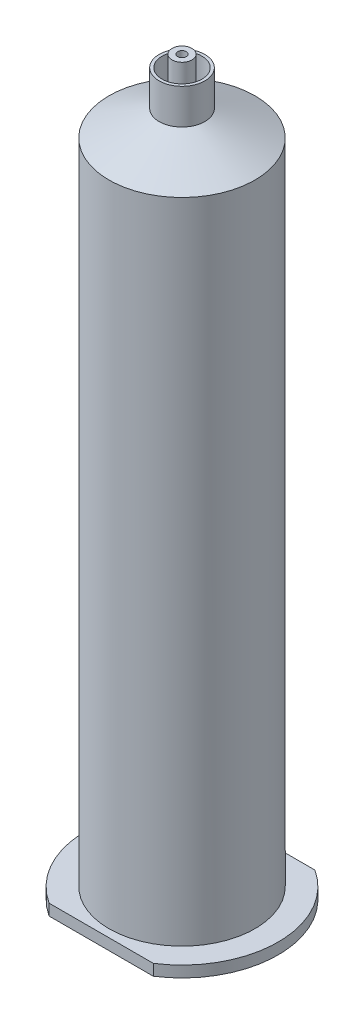
SolidWorks part; units mm, degrees
material "ABS"
ref_plane "Front Plane" through (0, 0, 0) normal (0, 0, 1) x (1, 0, 0)
ref_plane "Top Plane" through (0, 0, 0) normal (0, 1, 0) x (1, 0, 0)
ref_plane "Right Plane" through (0, 0, 0) normal (1, 0, 0) x (0, 0, -1)
sketch "Sketch3" plane through (0, 0, 0) normal (0, 1, 0) x (1, 0, 0)
  line L1 (-16.6, 16.6) -> (16.6, 16.6) construction
  line L2 (-16.6, 16.6) -> (-16.6, -16.6) construction
  line L3 (-16.6, -16.6) -> (16.6, -16.6) construction
  line L4 (16.6, 16.6) -> (16.6, -16.6) construction
  line L5 (-16.6, 16.6) -> (16.6, -16.6) construction
  line L6 (-16.6, -16.6) -> (16.6, 16.6) construction
  line L8 (-10.7006, 16.6) -> (10.7006, 16.6)
  line L9 (0, 0) -> (0, 16.6) construction
  line L26 (-10.7006, -16.6) -> (10.7006, -16.6)
  arc A18 (-10.7006, 16.6) -> (-10.7006, -16.6) centre (0, 0) ccw
  arc A19 (10.7006, -16.6) -> (10.7006, 16.6) centre (0, 0) ccw
  point P0 (0, 0)
  dimension "D1" = 39.5
  dimension "D2" = 33.2
extrude "Boss-Extrude2" add sketch "Sketch3" along normal blind 1.3
sketch "Sketch4" plane through (0, 1.3, 0) normal (0, 1, 0) x (1, 0, 0)
  line L6 (10.7006, 16.6) -> (-10.7006, 16.6)
  line L7 (10.7006, 16.6) -> (-10.7006, 16.6)
  line L8 (-10.7006, -16.6) -> (10.7006, -16.6)
  line L9 (-10.7006, -16.6) -> (10.7006, -16.6)
  arc A6 (10.7006, -16.6) -> (10.7006, 16.6) centre (0, 0) ccw
  arc A7 (10.7006, -16.6) -> (10.7006, 16.6) centre (0, 0) ccw
  arc A8 (-10.7006, 16.6) -> (-10.7006, -16.6) centre (0, 0) ccw
  arc A9 (-10.7006, 16.6) -> (-10.7006, -16.6) centre (0, 0) ccw
  dimension "D1" = 0
extrude "Boss-Extrude3" add sketch "Sketch4" along normal blind 1
sketch "Sketch5" plane through (0, 0, 0) normal (0, -1, 0) x (1, 0, 0)
  circle A0 centre (0, 0) radius 15
  dimension "D1" = 30
extrude "Boss-Extrude4" add sketch "Sketch5" against normal blind 135.5 contours A0
fillet "Fillet1" [suppressed] radius 0.81
sketch "Sketch6" plane through (0, 0, 0) normal (0, -1, 0) x (1, 0, 0)
  circle A0 centre (0, 0) radius 13.75
  dimension "D1" = 27.5
extrude "Cut-Extrude2" cut sketch "Sketch6" against normal through all
sketch "Sketch7" plane through (0, 135.5, 0) normal (0, 1, 0) x (1, 0, 0)
  circle A0 centre (0, 0) radius 13.75 construction
  circle A1 centre (0, 0) radius 13.75
sketch "Sketch8" plane through (0, 135.5, 0) normal (0, 1, 0) x (1, 0, 0)
  circle A0 centre (0, 0) radius 15 construction
  circle A1 centre (0, 0) radius 15
ref_plane "Plane2" through (0, 141.5, 0) normal (0, 1, 0) x (1, 0, 0)
sketch "Sketch9" plane through (0, 141.5, 0) normal (0, 1, 0) x (1, 0, 0)
  circle A0 centre (0, 0) radius 2.05
  dimension "D1" = 4.1
sketch "Sketch10" plane through (0, 141.5, 0) normal (0, 1, 0) x (1, 0, 0)
  circle A0 centre (0, 0) radius 0.9
  dimension "D1" = 1.8
loft "Loft1" add profiles "Sketch9", "Sketch8" connector at (-0.9604, 141.5, 1.8111) connector at (-13.8292, 135.5, 5.8098)
loft "Cut-Loft1" cut profiles "Sketch7", "Sketch10" connector at (0, 135.5, 13.75) connector at (0, 141.5, 0.9)
ref_plane "Plane4" through (0, 140.75, 0) normal (0, 1, 0) x (1, 0, 0)
sketch "Sketch11" plane through (0, 140.75, 0) normal (0, 1, 0) x (1, 0, 0)
  circle A0 centre (0, 0) radius 4.7
  circle A1 centre (0, 0) radius 4.1
  dimension "D1" = 9.4
  dimension "D2" = 0.6
extrude "Boss-Extrude5" add sketch "Sketch11" along normal blind 7.25 separate body
sketch "Sketch12" plane through (0, 141.5, 0) normal (0, 1, 0) x (1, 0, 0)
  circle A0 centre (0, 0) radius 0.9 construction
  circle A1 centre (0, 0) radius 2.05
  circle A2 centre (0, 0) radius 2.05
  circle A3 centre (0, 0) radius 0.9
  dimension "D1" = 0
extrude "Boss-Extrude6" add sketch "Sketch12" along normal offset from surface (8.9 mm away) 2.4 up to face at (0, 148, 4.7) offset beyond the face yes
ref_axis "Axis1" through (0, 135.5, 0) along (0, -1, 0)
ref_plane "Plane5" through (0, 135.5, 0) normal (0, 1, 0) x (1, 0, 0)
